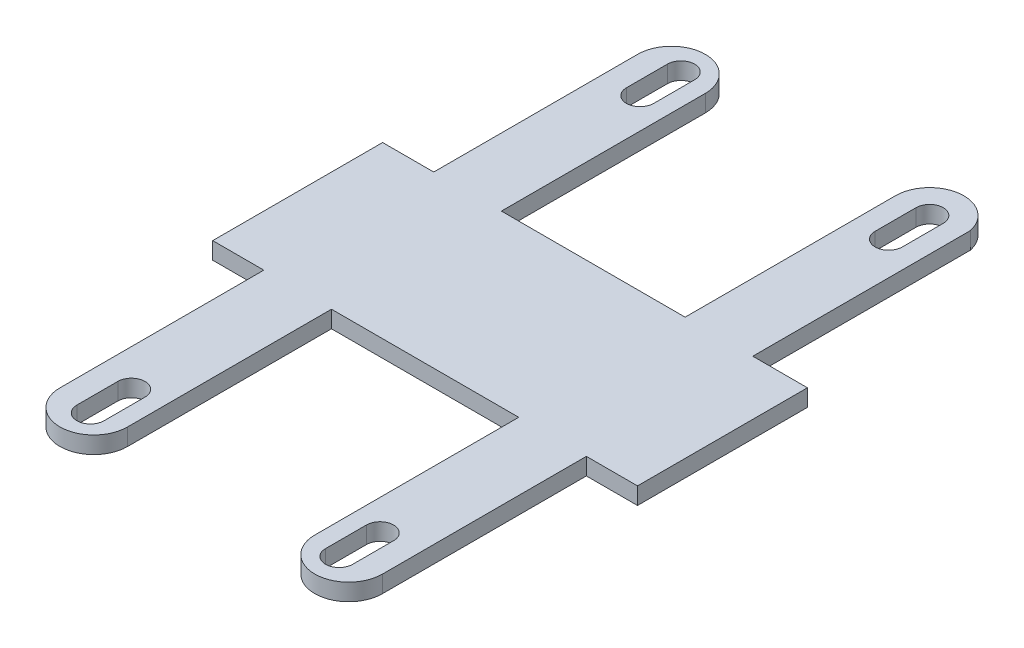
SolidWorks part; units mm, degrees
ref_plane "Front Plane" through (0, 0, 0) normal (0, 0, 1) x (1, 0, 0)
ref_plane "Top Plane" through (0, 0, 0) normal (0, 1, 0) x (1, 0, 0)
ref_plane "Right Plane" through (0, 0, 0) normal (1, 0, 0) x (0, 0, -1)
sketch "Sketch1" plane through (0, 0, 0) normal (0, 1, 0) x (1, 0, 0)
  line L0 (21.2225, 23.9449) -> (27.6545, 23.9449)
  line L1 (-22.3455, 23.9449) -> (-16.3274, 23.9449)
  line L2 (-22.3455, 23.9449) -> (-22.3455, 3.9449)
  line L3 (-22.3455, 3.9449) -> (-16.3274, 3.9449)
  line L4 (27.6545, 23.9449) -> (27.6545, 3.9449)
  line L5 (-16.3274, 23.9449) -> (-16.3274, 47.9433)
  line L6 (-8.3636, 23.9449) -> (-8.3636, 47.9433)
  line L7 (2.6545, 23.9449) -> (2.6545, 3.9449) construction
  line L8 (-8.3636, 3.9449) -> (13.6726, 3.9449)
  line L9 (21.2225, 23.9449) -> (21.2225, 49.5511)
  line L10 (13.2588, 23.9449) -> (13.2588, 48.6969)
  line L11 (-22.3455, 13.9449) -> (27.6545, 13.9449) construction
  line L12 (21.6364, 3.9449) -> (27.6545, 3.9449)
  line L13 (-16.3274, 3.9449) -> (-16.3274, -20.0536)
  line L14 (-8.3636, 3.9449) -> (-8.3636, -20.0536)
  line L15 (17.2865, 48.6969) -> (17.2865, 43.8803) construction
  line L16 (21.6364, 3.9449) -> (21.6364, -20.0536)
  line L17 (13.6726, 3.9449) -> (13.6726, -20.0536)
  line L18 (-8.3636, 23.9449) -> (13.2588, 23.9449)
  line L19 (18.8865, 48.6969) -> (18.8865, 43.8803)
  line L20 (15.6865, 48.6969) -> (15.6865, 43.8803)
  line L21 (-11.9775, 48.6969) -> (-11.9775, 43.8803) construction
  line L22 (-13.5775, 48.6969) -> (-13.5775, 43.8803)
  line L23 (-10.3775, 48.6969) -> (-10.3775, 43.8803)
  line L24 (-11.9775, -20.8072) -> (-11.9775, -15.9906) construction
  line L25 (-13.5775, -20.8072) -> (-13.5775, -15.9906)
  line L26 (-10.3775, -20.8072) -> (-10.3775, -15.9906)
  line L27 (17.2865, -20.8072) -> (17.2865, -15.9906) construction
  line L28 (18.8865, -20.8072) -> (18.8865, -15.9906)
  line L29 (15.6865, -20.8072) -> (15.6865, -15.9906)
  arc A0 (18.8865, 48.6969) -> (15.6865, 48.6969) centre (17.2865, 48.6969) ccw
  arc A1 (-8.3636, 47.9433) -> (-16.3274, 47.9433) centre (-12.3455, 47.9433) ccw
  arc A2 (15.6865, 43.8803) -> (18.8865, 43.8803) centre (17.2865, 43.8803) ccw
  arc A3 (13.2588, 48.6969) -> (21.2225, 49.5511) centre (17.2865, 48.6969) cw
  arc A4 (-13.5775, 48.6969) -> (-10.3775, 48.6969) centre (-11.9775, 48.6969) cw
  arc A5 (-8.3636, -20.0536) -> (-16.3274, -20.0536) centre (-12.3455, -20.0536) cw
  arc A6 (-10.3775, 43.8803) -> (-13.5775, 43.8803) centre (-11.9775, 43.8803) cw
  arc A7 (13.6726, -20.0536) -> (21.6364, -20.0536) centre (17.6545, -20.0536) ccw
  arc A8 (-13.5775, -20.8072) -> (-10.3775, -20.8072) centre (-11.9775, -20.8072) ccw
  arc A9 (-10.3775, -15.9906) -> (-13.5775, -15.9906) centre (-11.9775, -15.9906) ccw
  arc A10 (18.8865, -20.8072) -> (15.6865, -20.8072) centre (17.2865, -20.8072) cw
  arc A11 (15.6865, -15.9906) -> (18.8865, -15.9906) centre (17.2865, -15.9906) cw
  point P4 (17.2865, 46.2886)
  point P6 (-12.3455, 35.9441)
  point P15 (17.6545, 35.9441)
  point P24 (-12.3455, -8.0544)
  point P31 (17.6545, -8.0544)
  point P40 (-11.9775, 46.2886)
  point P47 (-11.9775, -18.3989)
  point P54 (17.2865, -18.3989)
  dimension "D1" = 50
  dimension "D2" = 20
extrude "Boss-Extrude1" add sketch "Sketch1" along normal blind 2
